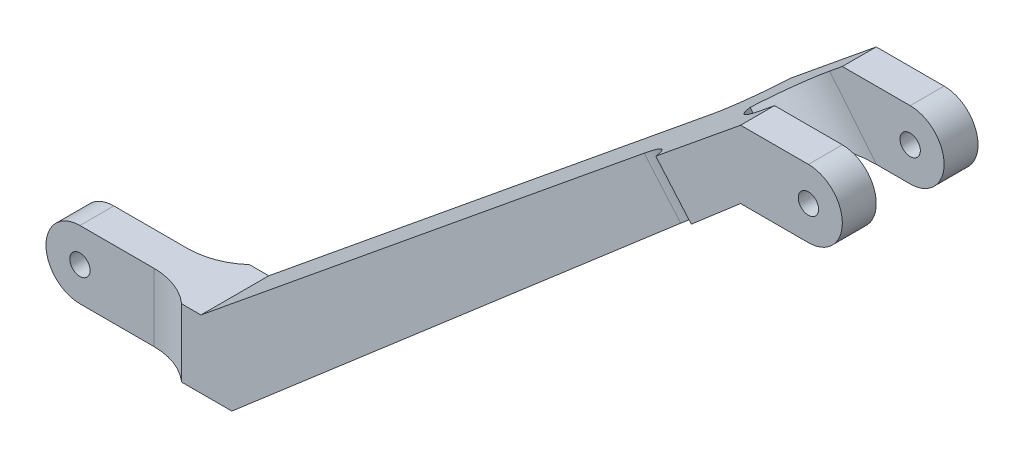
SolidWorks part; units mm, degrees
ref_plane "Alzado" through (0, 0, 0) normal (0, 0, 1) x (1, 0, 0)
ref_plane "Planta" through (0, 0, 0) normal (0, 1, 0) x (1, 0, 0)
ref_plane "Vista lateral" through (0, 0, 0) normal (1, 0, 0) x (0, 0, -1)
sketch "Croquis1" plane through (0, 0, 0) normal (0, 0, 1) x (1, 0, 0)
  line L0 (0, -5) -> (-10, -5)
  line L1 (0, 5) -> (-10, 5)
  line L4 (-90, -74) -> (-114.8955, -74)
  line L5 (-10, 5) -> (-10, -5) construction
  line L6 (-114.8955, -64) -> (-94.5563, -64)
  line L7 (-114.8955, -69) -> (-106.9391, -69) construction
  line L8 (-90, -74) -> (-10, -5)
  line L9 (-94.5563, -64) -> (-10, 5)
  circle A0 centre (0, 0) radius 1.5
  arc A1 (0, -5) -> (0, 5) centre (0, 0) ccw
  arc A2 (-114.8955, -64) -> (-114.8955, -74) centre (-114.8955, -69) ccw
  circle A3 centre (-114.8955, -69) radius 1.5
  dimension "D1" = 3
  dimension "D2" = 10
  dimension "D5" = 3
  dimension "D3" = 10
  dimension "D4" = 114.8955
  dimension "D8" = 69
  dimension "D10" = 10
extrude "Saliente-Extruir1" add sketch "Croquis1" along normal blind 10
sketch "Croquis2" plane through (0, -64, 0) normal (0, 1, 0) x (1, 0, 0)
  line L0 (-119.8955, 0) -> (-119.8955, -10) construction
  line L1 (-142.3955, -2.5) -> (-142.3955, 7.5812)
  line L2 (-142.3955, -7.5) -> (-97.3955, -7.5)
  line L3 (-97.3955, -2.5) -> (-97.3955, 7.5812)
  line L4 (-142.3955, -2.5) -> (-97.3955, -2.5)
  line L6 (-142.3955, -7.5) -> (-97.3955, -2.5) construction
  line L7 (-142.3955, -2.5) -> (-97.3955, -7.5) construction
  line L8 (-142.3955, -17.5812) -> (-97.3955, -17.5812)
  line L9 (-142.3955, -17.5812) -> (-142.3955, -7.5)
  line L10 (-142.3955, 7.5812) -> (-97.3955, 7.5812)
  line L11 (-97.3955, -17.5812) -> (-97.3955, -7.5)
  line L12 (-142.3955, -17.5812) -> (-97.3955, 7.5812) construction
  line L13 (-142.3955, 7.5812) -> (-97.3955, -17.5812) construction
  point P4 (-119.8955, -5)
  point P9 (-119.8955, -5)
  dimension "D1" = 5
  dimension "D2" = 45
extrude "Cortar-Extruir1" cut sketch "Croquis2" against normal blind 50
ref_plane "Plano1" through (0, 0, 5) normal (0, 0, 1) x (1, 0, 0)
sketch "Croquis3" plane through (0, 0, 5) normal (0, 0, 1) x (1, 0, 0)
  line L0 (-10, -5) -> (0, -5) construction
  line L1 (0, 5) -> (-10, 5)
  line L3 (0, -5) -> (-10, -5)
  line L4 (-10, 5) -> (-10, -5)
  arc A0 (0, -5) -> (0, 5) centre (0, 0) ccw construction
  arc A1 (0, -5) -> (0, 5) centre (0, 0) ccw
  circle A2 centre (0, 0) radius 1.5 construction
  circle A3 centre (0, 0) radius 1.5
  dimension "D1" = 10
extrude "Saliente-Extruir2" add sketch "Croquis3" along normal mid plane 20
sketch "Croquis4" plane through (0, 5, 0) normal (0, 1, 0) x (1, 0, 0)
  line L0 (5, 5) -> (5, -15) construction
  line L1 (0, -15) -> (5, -15) construction
  line L3 (-7.5, -10) -> (17.5, -10)
  line L4 (-7.5, -10) -> (-7.5, 0)
  line L5 (-7.5, 0) -> (17.5, 0)
  line L6 (17.5, -10) -> (17.5, 0)
  line L7 (-7.5, -10) -> (17.5, 0) construction
  line L8 (-7.5, 0) -> (17.5, -10) construction
  point P5 (5, -5)
  dimension "D1" = 10
  dimension "D2" = 25
extrude "Cortar-Extruir2" cut sketch "Croquis4" against normal blind 50
sketch "Croquis5" plane through (0, 0, 5) normal (0, 0, 1) x (1, 0, 0)
  line L1 (-22.5, -5.2003) -> (-17.2669, -11.2677)
  line L6 (-90, -74) -> (-10, -5)
  line L7 (-10, -5) -> (-10, 5)
  line L8 (-10, 5) -> (-94.5563, -64)
  line L9 (-94.5563, -64) -> (-97.3955, -64)
  line L10 (-97.3955, -64) -> (-97.3955, -74)
  line L11 (-97.3955, -74) -> (-90, -74)
  line L12 (-17.2669, -11.2677) -> (-10, -5)
  line L13 (-10, -5) -> (-10, 5)
  line L14 (-10, 5) -> (-22.5, -5.2003)
  dimension "D2" = 22.5
  dimension "D1" = 0
extrude "Saliente-Extruir3" add sketch "Croquis5" along normal mid plane 20
sketch "Croquis7" plane through (-6.4464, 7.8998, 0) normal (-0.6322, 0.7748, 0) x (0.7748, 0.6322, 0)
  line L1 (5, -10) -> (-17, -10)
  line L2 (5, -10) -> (5, 0)
  line L3 (5, 0) -> (-17, 0)
  line L4 (-17, -10) -> (-17, 0)
  dimension "D1" = 22
extrude "Cortar-Extruir4" cut sketch "Croquis7" against normal blind 20
fillet "Redondeo1" radius 10 6 edges at (-19.8834, -8.234, 0) (-97.3955, -69, 2.5) (-97.3955, -69, 7.5) (-19.8834, -8.234, 10) (-17.1159, -5.914, 0) (-17.1159, -5.914, 10)
